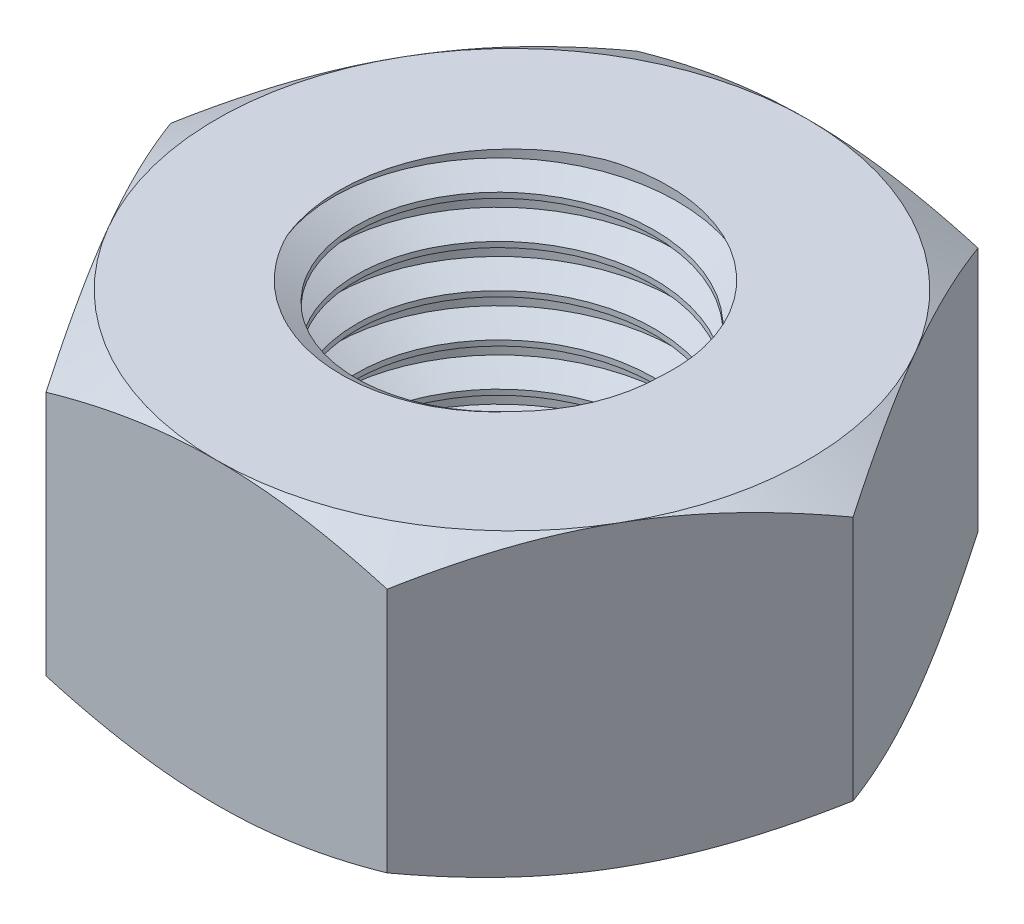
SolidWorks part; units mm, degrees
ref_plane "Front Plane" through (0, 0, 0) normal (0, 0, 1) x (1, 0, 0)
ref_plane "Top Plane" through (0, 0, 0) normal (0, 1, 0) x (1, 0, 0)
ref_plane "Right Plane" through (0, 0, 0) normal (1, 0, 0) x (0, 0, -1)
sketch "Sketch1" plane through (0, 0, 0) normal (0, 1, 0) x (1, 0, 0)
  line L1 (16, 0) -> (8, 13.8564)
  line L2 (8, 13.8564) -> (-8, 13.8564)
  line L3 (-8, 13.8564) -> (-16, 0)
  line L4 (-16, 0) -> (-8, -13.8564)
  line L5 (-8, -13.8564) -> (8, -13.8564)
  line L6 (8, -13.8564) -> (16, 0)
  circle A0 centre (0, 0) radius 13.8564 construction
  dimension "D1" = 32
extrude "Boss-Extrude1" add sketch "Sketch1" along normal mid plane 14
hole_wizard "M16x2.0 Tapped Hole1" positions "Sketch2" profile "Sketch3" tap size "M16x2.0" standard "ANSI Metric" end condition through all
sketch "Sketch2" plane through (0, 7, 0) normal (0, 1, 0) x (1, 0, 0)
  point P0 (0, 0)
sketch "Sketch3" plane through (0, 7, 0) normal (1, 0, 0) x (0, 0, 1)
  line L0 (0, 0) -> (0, 14)
  line L1 (0, 14) -> (7, 14)
  line L2 (7, 14) -> (7, 0)
  line L5 (7, 0) -> (0, 0)
  line L11 (0, -6.35) -> (0, 107.95) construction
  dimension "Thru Tap Drill Dia." = 14
  dimension "Thru Tap Drill Depth" = 14
cosmetic thread "Hole Thread1" parameters "D2"=16
thread "Thread1" pitch 2 method cut profile "Thread Profile1" start angle 0, offset 3, length 20, pitch 2, diameter 14
ref_plane "Plane1" through (-7, 10, 0) normal (0, 0, -1) x (1, 0, 0)
sketch "Thread Profile1" plane through (-7, 10, 0) normal (0, 0, -1) x (1, 0, 0)
  line L0 (0, 0) -> (0, 2) construction
  line L11 (0, 0) -> (0, 1.75)
  line L12 (0, 1.75) -> (-1.0825, 1.125)
  line L13 (-1.0825, 1.125) -> (-1.0825, 0.625)
  line L15 (-1.0825, 0.625) -> (0, 0)
  line L17 (-1.0825, 0.875) -> (0, 0.875) construction
  point P2 (0, 0)
  dimension "Pitch" = 2
  dimension "Profile_Angle" = 60
  dimension "Profile_Land" = 0.5
  dimension "Profile_Height" = 1.0825
sketch "Sketch7" plane through (0, 0, 0) normal (1, 0, 0) x (0, 0, -1)
  line L0 (13.8564, 7) -> (22.0883, 7)
  line L1 (22.0883, 7) -> (22.0883, 2.2473)
  line L2 (22.0883, 2.2473) -> (13.8564, 7)
  line L3 (0, 0) -> (0, 10.5191) construction
  dimension "D1" = 30
revolve "Cut-Revolve1" cut sketch "Sketch7" angle 360 about L3
mirror "Mirror1" about plane through (0, 0, 0) normal (0, 1, 0) of "Cut-Revolve1"
